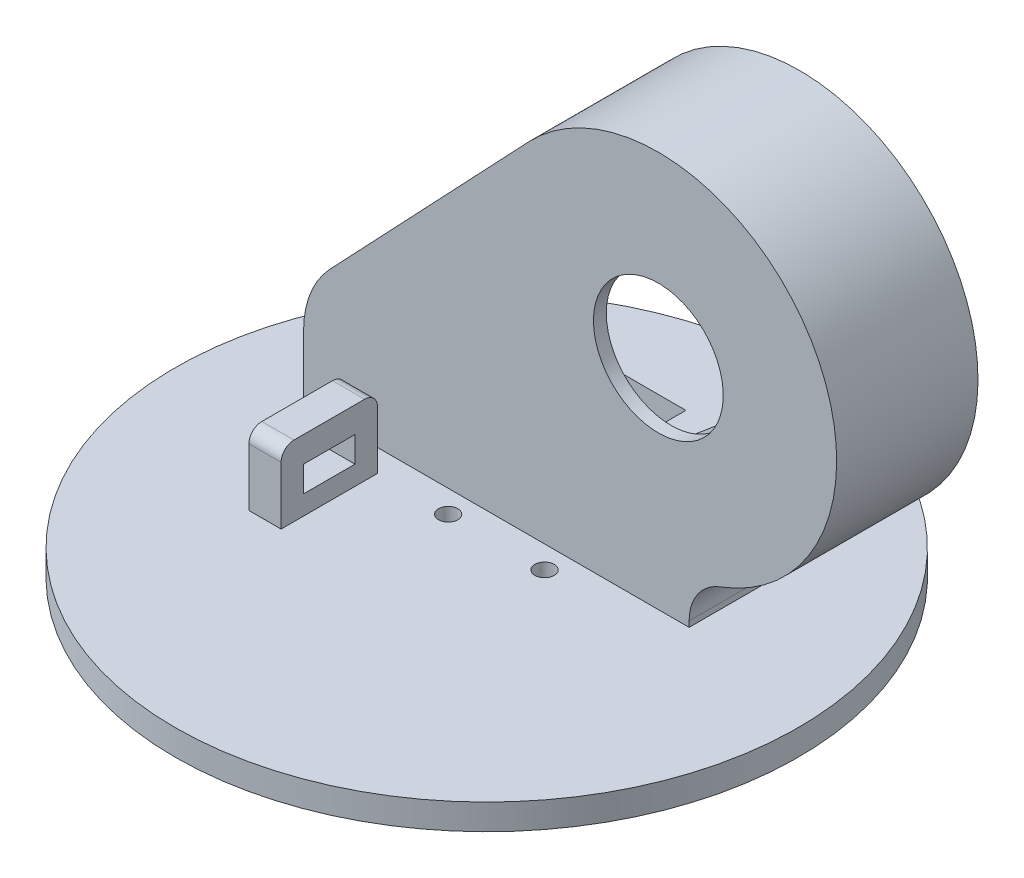
SolidWorks part; units mm, degrees
material "ABS"
ref_plane "Front Plane" through (0, 0, 0) normal (0, 0, 1) x (1, 0, 0)
ref_plane "Top Plane" through (0, 0, 0) normal (0, 1, 0) x (1, 0, 0)
ref_plane "Right Plane" through (0, 0, 0) normal (1, 0, 0) x (0, 0, -1)
sketch "Sketch1" plane through (0, 0, 0) normal (0, 1, 0) x (1, 0, 0)
  line L0 (-25.5, 4.5) -> (18.5, 4.5) construction
  line L1 (-33.5, 26.5) -> (-25.5, 26.5) construction
  line L2 (-33.5, 26.5) -> (-33.5, 4.5) construction
  line L3 (-33.5, 4.5) -> (-25.5, 4.5) construction
  line L4 (-25.5, 26.5) -> (-25.5, 4.5) construction
  line L5 (-33.5, 26.5) -> (-25.5, 4.5) construction
  line L6 (-33.5, 4.5) -> (-25.5, 26.5) construction
  line L7 (26.5, 26.5) -> (18.5, 26.5) construction
  line L8 (26.5, 26.5) -> (26.5, 4.5) construction
  line L9 (26.5, 4.5) -> (18.5, 4.5) construction
  line L10 (18.5, 26.5) -> (18.5, 4.5) construction
  line L11 (26.5, 26.5) -> (18.5, 4.5) construction
  line L12 (26.5, 4.5) -> (18.5, 26.5) construction
  line L13 (-7.5, 1.5) -> (7.5, 1.5) construction
  line L15 (-23.5, 1.5) -> (-18.5, 1.5)
  line L16 (-23.5, 1.5) -> (-23.5, -13.5)
  line L17 (-23.5, -13.5) -> (-18.5, -13.5)
  line L18 (-18.5, 1.5) -> (-18.5, -13.5)
  line L19 (-23.5, 1.5) -> (-18.5, -13.5) construction
  line L20 (-23.5, -13.5) -> (-18.5, 1.5) construction
  circle A0 centre (0, 0) radius 48.5
  circle A1 centre (7.5, 1.5) radius 1.5
  circle A2 centre (-7.5, 1.5) radius 1.5
  point P7 (-29.5, 15.5)
  point P12 (22.5, 15.5)
  point P13 (0, 48.5)
  point P14 (22.5, 26.5)
  point P19 (0, 1.5)
  point P20 (-48.5, 0)
  point P25 (-21, -6)
  dimension "D1" = 97
  dimension "D8" = 3
  dimension "D2" = 22
  dimension "D3" = 22
  dimension "D4" = 8
  dimension "D5" = 22
  dimension "D6" = 15
  dimension "D7" = 3
  dimension "D9" = 10
  dimension "D10" = 5
  dimension "D11" = 60
  dimension "D12" = 15
  dimension "D13" = 15
extrude "Boss-Extrude1" add sketch "Sketch1" along normal blind 4
extrude "Boss-Extrude2" add sketch "Sketch1<4>" along normal blind 15 contours L16 L17 L18 L15
sketch "Sketch1<4>" plane through (0, 0, 0) normal (0, 1, 0) x (1, 0, 0) same geometry as "Sketch1"
fillet "Fillet1" radius 2 2 edges at (-21, 15, -1.5) (-21, 15, 13.5)
ref_plane "Plane1" through (0, 0, -16) normal (0, 0, 1) x (1, 0, 0)
sketch "Sketch3" plane through (0, 0, -16) normal (0, 0, 1) x (1, 0, 0)
  line L0 (-33.5, 0) -> (-33.5, 14.0208)
  line L1 (-29.3868, 24.3396) -> (1.5696, 57)
  line L2 (26.5, 10) -> (26.5, 0)
  line L3 (48.5, 4) -> (-48.5, 4) construction
  line L4 (-33.5, 0) -> (26.5, 0)
  arc A0 (1.5696, 57) -> (30.0613, 11.4466) centre (21.7102, 37.9102) cw
  arc A1 (30.0613, 11.4466) -> (26.5, 10) centre (37.2839, -11.4408) ccw
  arc A2 (-33.5, 14.0208) -> (-29.3868, 24.3396) centre (-18.5, 14.0208) cw
  circle A3 centre (21.7102, 37.9102) radius 10.1
  point P12 (-33.5, 20)
  dimension "D2" = 15
  dimension "D5" = 27.75
  dimension "D6" = 24
  dimension "D8" = 20.2
  dimension "D1" = 20
  dimension "D3" = 45
  dimension "D4" = 53
  dimension "D7" = 60
  dimension "D9" = 10
extrude "Extrude-Thin1" add sketch "Sketch3" against normal mid plane 22 thin contours L0 A2 L1 A0 A1 L2 thin type one direction wall 10
extrude "Boss-Extrude3" add sketch "Sketch3<4>" along normal up to surface (11 mm away) up to face at (2.4745, 20.1497, -5)
sketch "Sketch3<4>" plane through (0, 0, -16) normal (0, 0, 1) x (1, 0, 0) same geometry as "Sketch3"
sketch "Sketch5" plane through (0, 0, -27) normal (0, 0, -1) x (-1, 0, 0)
  line L1 (-16.5, 4) -> (25.5, 4)
  line L8 (-16.5, 4) -> (-26.5, 4) construction
  line L9 (33.5, 4) -> (23.5, 4) construction
  line L11 (30.5, 4) -> (30.5, 14.0208)
  line L12 (27.2094, 22.2759) -> (-3.747, 54.9362)
  line L13 (-23.5, 11.7757) -> (-23.5, 4)
  line L15 (16.097, 34) -> (-3.747, 54.9362)
  line L17 (48.5, 4) -> (-48.5, 4) construction
  line L18 (33.5, 4) -> (33.5, 14.0208) construction
  arc A15 (-29.1585, 14.3076) -> (-16.5, 4) centre (-35.819, -6.7986) cw
  arc A16 (16.097, 34) -> (25.5, 4) centre (-9.8706, 9.3873) cw
  arc A19 (30.5, 14.0208) -> (27.2094, 22.2759) centre (18.5, 14.0208) ccw
  arc A20 (-23.5, 11.7757) -> (-29.1585, 14.3076) centre (-37.2839, -11.4408) ccw
  arc A21 (-3.747, 54.9362) -> (-29.1585, 14.3076) centre (-21.7102, 37.9102) ccw
  arc A24 (-3.747, 54.9362) -> (-29.1585, 14.3076) centre (-21.7102, 37.9102) ccw
  dimension "D3" = 30
  dimension "D2" = 10
  dimension "D4" = 8
  dimension "D1" = 3
extrude "Cut-Extrude2" cut sketch "Sketch5" against normal blind 11
sketch "Sketch8" plane through (0, 0, -16) normal (0, 0, -1) x (-1, 0, 0)
  line L0 (-37.2073, 36.5544) -> (-23.066, 53.4074)
  line L1 (-37.2073, 36.5544) -> (-5.0335, 9.5573)
  line L2 (-23.066, 53.4074) -> (9.1079, 26.4103)
  line L3 (-5.0335, 9.5573) -> (9.1079, 26.4103)
  line L4 (-5.0335, 9.5573) -> (25.8487, 9.5573) construction
  line L5 (-35.6487, 43.079) -> (-29.2209, 50.7395) construction
  line L6 (-21.1204, 23.0559) -> (-6.9791, 39.9088) construction
  circle A0 centre (-35.6487, 43.079) radius 1.5
  circle A1 centre (-29.2209, 50.7395) radius 1.5
  circle A2 centre (7.5493, 19.8857) radius 1.5
  circle A3 centre (1.1214, 12.2252) radius 1.5
  point P0 (-21.7102, 37.9102)
  dimension "D6" = 3
  dimension "D2" = 42
  dimension "D3" = 22
  dimension "D4" = 11
  dimension "D5" = 14
  dimension "D7" = 6
  dimension "D8" = 10
  dimension "D9" = 6
  dimension "D10" = 3
  dimension "D11" = 50
  dimension "D12" = 11
extrude "Cut-Extrude3" cut sketch "Sketch8" against normal blind 9
sketch "Sketch9" plane through (-23.5, 0, 0) normal (-1, 0, 0) x (0, 0, 1)
  line L0 (-1.5, 13) -> (-1.5, 4) construction
  line L1 (2, 11) -> (10, 11)
  line L2 (2, 11) -> (2, 7)
  line L3 (2, 7) -> (10, 7)
  line L4 (10, 11) -> (10, 7)
  line L5 (2, 11) -> (10, 7) construction
  line L6 (2, 7) -> (10, 11) construction
  line L7 (13.5, 13) -> (13.5, 4) construction
  line L8 (0.5, 15) -> (11.5, 15) construction
  point P4 (6, 9)
  dimension "D1" = 8
  dimension "D2" = 3.5
  dimension "D3" = 3.5
  dimension "D4" = 4
  dimension "D5" = 4
extrude "Cut-Extrude4" cut sketch "Sketch9" against normal through all both and the other way through all
sketch "Sketch10" plane through (0, 4, 0) normal (0, 1, 0) x (1, 0, 0)
  line L0 (-25.5, 16) -> (16.5, 16) construction
  line L1 (-3, 34) -> (-18, 34)
  line L2 (-3, 34) -> (-3, 24)
  line L3 (-3, 24) -> (-18, 24)
  line L4 (-18, 34) -> (-18, 24)
  line L5 (-3, 34) -> (-18, 24) construction
  line L6 (-3, 24) -> (-18, 34) construction
  line L7 (-25.5, 16) -> (-25.5, 27) construction
  point P0 (-10.5, 29)
  dimension "D1" = 8
  dimension "D2" = 15
  dimension "D3" = 10
  dimension "D4" = 15
extrude "Cut-Extrude5" cut sketch "Sketch10" against normal through all
fillet "Fillet2" radius 7.5 1 edges at (26.5, 10, -16)
sketch "Sketch11" plane through (0, 0, -16) normal (0, 0, -1) x (-1, 0, 0)
  line L0 (-5.0335, 9.5573) -> (9.1079, 26.4103) construction
  line L1 (9.1079, 26.4103) -> (-23.066, 53.4074) construction
  line L2 (-16.5, 4) -> (25.5, 4)
  line L3 (16.097, 34) -> (-3.747, 54.9362)
  line L4 (-16.5, 4) -> (25.5, 4)
  line L5 (16.097, 34) -> (-3.747, 54.9362)
  line L6 (-37.2073, 36.5544) -> (-5.0335, 9.5573) construction
  line L7 (-23.066, 53.4074) -> (-37.2073, 36.5544) construction
  line L8 (-5.0335, 9.5573) -> (9.1079, 26.4103)
  line L9 (9.1079, 26.4103) -> (-23.066, 53.4074)
  line L10 (-37.2073, 36.5544) -> (-5.0335, 9.5573)
  line L11 (-23.066, 53.4074) -> (-37.2073, 36.5544)
  circle A0 centre (1.1214, 12.2252) radius 1.5 construction
  circle A1 centre (7.5493, 19.8857) radius 1.5 construction
  circle A2 centre (-35.6487, 43.079) radius 1.5 construction
  arc A3 (25.5, 4) -> (16.097, 34) centre (-9.8706, 9.3873) ccw
  arc A4 (-3.747, 54.9362) -> (-29.1585, 14.3076) centre (-21.7102, 37.9102) ccw
  arc A5 (-16.5, 4) -> (-29.1585, 14.3076) centre (-35.819, -6.7986) ccw
  arc A6 (25.5, 4) -> (16.097, 34) centre (-9.8706, 9.3873) ccw
  arc A7 (-3.747, 54.9362) -> (-29.1585, 14.3076) centre (-21.7102, 37.9102) ccw
  arc A8 (-16.5, 4) -> (-29.1585, 14.3076) centre (-35.819, -6.7986) ccw
  circle A9 centre (-29.2209, 50.7395) radius 1.5 construction
  circle A10 centre (1.1214, 12.2252) radius 1.5
  circle A11 centre (7.5493, 19.8857) radius 1.5
  circle A12 centre (-35.6487, 43.079) radius 1.5
  circle A13 centre (-29.2209, 50.7395) radius 1.5
  dimension "D1" = 0
extrude "Boss-Extrude4" add sketch "Sketch11" along normal blind 2.5
